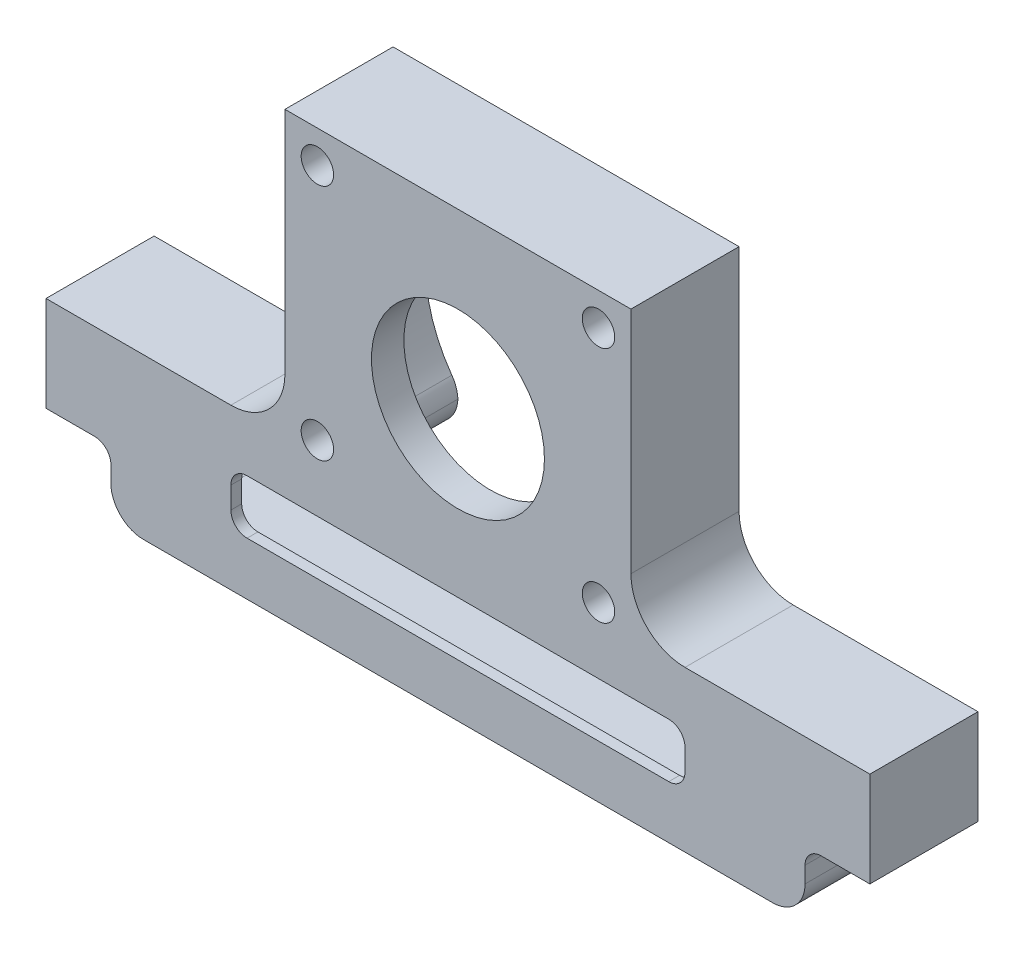
SolidWorks part; units mm, degrees
material "1060 Alloy"
ref_plane "Front Plane" through (0, 0, 0) normal (0, 0, 1) x (1, 0, 0)
ref_plane "Top Plane" through (0, 0, 0) normal (0, 1, 0) x (1, 0, 0)
ref_plane "Right Plane" through (0, 0, 0) normal (1, 0, 0) x (0, 0, -1)
sketch "Sketch1" plane through (0, 0, 0) normal (0, 0, 1) x (1, 0, 0)
  line L0 (-16, 38) -> (16, 38)
  line L1 (-20.1, 6.5) -> (20.1, 6.5) construction
  line L2 (-20.1, 6.5) -> (-20.1, 2.3) construction
  line L3 (-20.1, 2.3) -> (20.1, 2.3) construction
  line L4 (20.1, 6.5) -> (20.1, 2.3) construction
  line L5 (-20.1, 6.5) -> (20.1, 2.3) construction
  line L6 (-20.1, 2.3) -> (20.1, 6.5) construction
  line L7 (-26.1, 7) -> (26.1, 7) construction
  line L8 (-26.1, 7) -> (-26.1, 1.8) construction
  line L9 (-26.1, 1.8) -> (26.1, 1.8) construction
  line L10 (26.1, 7) -> (26.1, 1.8) construction
  line L11 (-26.1, 7) -> (26.1, 1.8) construction
  line L12 (-26.1, 1.8) -> (26.1, 7) construction
  line L13 (29.1, 9.8) -> (-29.1, 9.8) construction
  line L14 (29.1, 9.8) -> (29.1, -1) construction
  line L15 (29.1, -1) -> (-29.1, -1) construction
  line L16 (-29.1, 9.8) -> (-29.1, -1) construction
  line L17 (29.1, 9.8) -> (-29.1, -1) construction
  line L18 (29.1, -1) -> (-29.1, 9.8) construction
  line L19 (32.1, 11.8) -> (-32.1, 11.8) construction
  line L20 (32.1, 11.8) -> (32.1, -3) construction
  line L21 (32.1, -3) -> (-32.1, -3) construction
  line L22 (-32.1, 11.8) -> (-32.1, -3) construction
  line L23 (32.1, 11.8) -> (-32.1, -3) construction
  line L24 (32.1, -3) -> (-32.1, 11.8) construction
  line L25 (16, 38) -> (16, 11.8)
  line L26 (-16, 38) -> (-16, 11.8)
  line L27 (-16, 11.8) -> (-38.1, 11.8)
  line L28 (-38.1, 11.8) -> (-38.1, 3)
  line L29 (-38.1, 3) -> (-32.1, 3)
  line L30 (-32.1, 3) -> (-32.1, -3)
  line L31 (-32.1, -3) -> (32.1, -3)
  line L32 (32.1, -3) -> (32.1, 3)
  line L33 (32.1, 3) -> (38.1, 3)
  line L34 (38.1, 3) -> (38.1, 11.8)
  line L35 (38.1, 11.8) -> (16, 11.8)
  line L37 (-21, 6.9) -> (21, 6.9)
  line L38 (-21, 6.9) -> (-21, 1.9)
  line L39 (-21, 1.9) -> (21, 1.9)
  line L40 (21, 6.9) -> (21, 1.9)
  line L41 (-21, 6.9) -> (21, 1.9) construction
  line L42 (-21, 1.9) -> (21, 6.9) construction
  circle A0 centre (0, 22) radius 8
  circle A1 centre (0, 22) radius 13 construction
  point P2 (0, 4.4)
  point P5 (0, 4.4)
  point P13 (0, 4.4)
  point P18 (0, 4.4)
  point P34 (0, 4.4)
  dimension "D1" = 16
  dimension "D11" = 26
  dimension "D2" = 40.2
  dimension "D3" = 4.2
  dimension "D4" = 6
  dimension "D5" = 0.5
  dimension "D6" = 3
  dimension "D7" = 2.8
  dimension "D8" = 3
  dimension "D9" = 2
  dimension "D10" = 3
  dimension "D12" = 22
  dimension "D13" = 16
  dimension "D14" = 32
  dimension "D15" = 16
  dimension "D16" = 6
  dimension "D17" = 42
  dimension "D18" = 5
  dimension "D19" = 6
extrude "Boss-Extrude1" add sketch "Sketch1" along normal blind 10
fillet "Fillet1" radius 1.5 4 edges at (-21, 1.9, 5) (21, 1.9, 5) (21, 6.9, 5) (-21, 6.9, 5)
sketch "Sketch2" plane through (0, 0, 0) normal (0, 0, 1) x (1, 0, 0)
  circle A0 centre (0, 22) radius 13
  dimension "D1" = 26
extrude "Cut-Extrude1" cut sketch "Sketch2" along normal offset from surface (7 mm away) 3 up to face at (8, 22, 10)
sketch "Sketch3" plane through (0, 0, 0) normal (0, 0, 1) x (1, 0, 0)
  line L1 (-29.1, 9.9) -> (29.1, 9.9)
  line L2 (-29.1, 9.9) -> (-29.1, -1.1)
  line L3 (-29.1, -1.1) -> (29.1, -1.1)
  line L4 (29.1, 9.9) -> (29.1, -1.1)
  line L5 (-29.1, 9.9) -> (29.1, -1.1) construction
  line L6 (-29.1, -1.1) -> (29.1, 9.9) construction
  line L7 (0, 6.9) -> (0, 1.9) construction
  line L8 (19.5, 6.9) -> (-19.5, 6.9) construction
  line L9 (-19.5, 1.9) -> (19.5, 1.9) construction
  line L10 (-21, 4.4) -> (21, 4.4) construction
  line L11 (-21, 5.4) -> (-21, 3.4) construction
  line L12 (21, 3.4) -> (21, 5.4) construction
  line L14 (-20.1, 6.5) -> (20.1, 6.5) construction
  line L15 (-20.1, 6.5) -> (-20.1, 2.3) construction
  line L16 (-20.1, 2.3) -> (20.1, 2.3) construction
  line L17 (20.1, 6.5) -> (20.1, 2.3) construction
  line L18 (-20.1, 6.5) -> (20.1, 2.3) construction
  line L19 (-20.1, 2.3) -> (20.1, 6.5) construction
  point P0 (0, 4.4)
  point P17 (0, 4.4)
  dimension "D1" = 4.2
  dimension "D2" = 40.2
  dimension "D3" = 9
  dimension "D4" = 3.4
extrude "Cut-Extrude3" cut sketch "Sketch3" along normal offset from surface (7 mm away) 3 up to face at (8, 22, 10)
sketch "Sketch4" plane through (0, 0, 7) normal (0, 0, -1) x (-1, 0, 0)
  line L0 (-29.1, 9.9) -> (-4.7529, 9.9) construction
  line L1 (-26.1, 9.9) -> (26.1, 9.9)
  line L2 (-26.1, 9.9) -> (-26.1, -1.1)
  line L3 (-26.1, -1.1) -> (26.1, -1.1)
  line L4 (26.1, 9.9) -> (26.1, -1.1)
  line L5 (29.1, -1.1) -> (-29.1, -1.1) construction
  line L6 (-29.1, -1.1) -> (-29.1, 9.9) construction
  line L7 (29.1, 9.9) -> (29.1, -1.1) construction
  dimension "D1" = 3
  dimension "D2" = 3
extrude "Cut-Extrude4" cut sketch "Sketch4" against normal blind 2
sketch "Sketch5" plane through (0, 0, 0) normal (0, 0, -1) x (-1, 0, 0)
  line L0 (-16, 38) -> (16, 38) construction
  line L1 (-16, 11.8) -> (-16, 38) construction
  line L2 (16, 38) -> (16, 11.8) construction
  circle A0 centre (-13, 35) radius 1.5
  circle A1 centre (13, 35) radius 1.5
  circle A2 centre (-13, 13) radius 1.5
  circle A3 centre (13, 13) radius 1.5
  dimension "D1" = 3
  dimension "D5" = 25
  dimension "D2" = 3
  dimension "D3" = 3
  dimension "D4" = 3
extrude "Cut-Extrude7" cut sketch "Sketch5" against normal up to next
sketch "Sketch7" plane through (0, 0, 0) normal (0, 0, -1) x (-1, 0, 0)
  line L0 (26.1, 9.9) -> (-26.1, 9.9) construction
  line L1 (-10, 9.9) -> (10, 9.9)
  line L2 (-10, 9.9) -> (-10, 13.6934)
  line L3 (-10, 13.6934) -> (10, 13.6934)
  line L4 (10, 9.9) -> (10, 13.6934)
  line L5 (-16, 11.8) -> (-16, 38) construction
  line L6 (16, 38) -> (16, 11.8) construction
  circle A0 centre (0, 22) radius 13 construction
  dimension "D1" = 6
  dimension "D2" = 6
extrude "Cut-Extrude8" cut sketch "Sketch7" against normal up to surface (7 mm away) up to face at (8, 22, 7)
fillet "Fillet2" radius 1.5 8 edges at (-26.1, -1.1, 8) (-29.1, -1.1, 3.5) (-29.1, 9.9, 3.5) (-26.1, 9.9, 8) (26.1, -1.1, 8) (29.1, -1.1, 3.5) (26.1, 9.9, 8) (29.1, 9.9, 3.5)
fillet "Fillet3" radius 3 6 edges at (-32.1, -3, 5) (32.1, -3, 5) (10, 13.6934, 3.5) (-10, 13.6934, 3.5) (-10, 9.9, 3.5) (10, 9.9, 3.5)
fillet "Fillet4" radius 1.5 2 edges at (-32.1, 3, 5) (32.1, 3, 5)
fillet "Fillet5" radius 5 2 edges at (-16, 11.8, 5) (16, 11.8, 5)
